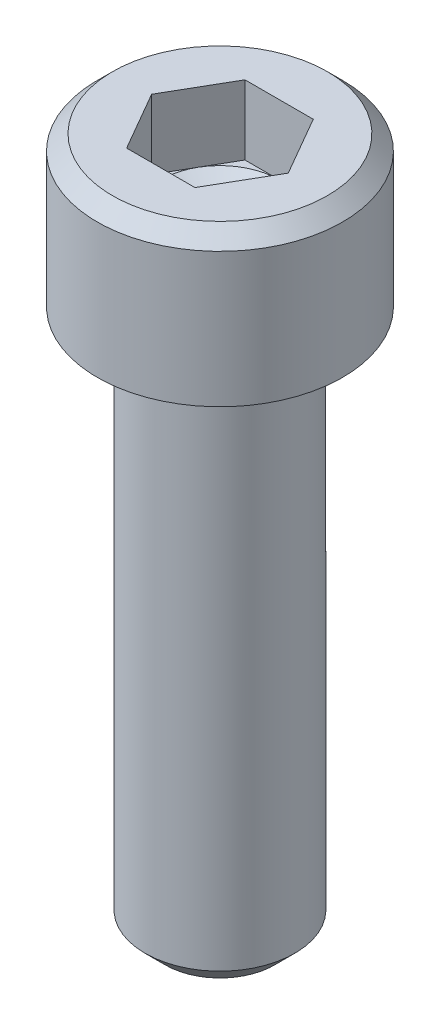
SolidWorks part; units mm, degrees
material "Alloy Steel"
ref_plane "Front Plane" through (0, 0, 0) normal (0, 0, 1) x (1, 0, 0)
ref_plane "Top Plane" through (0, 0, 0) normal (0, 1, 0) x (1, 0, 0)
ref_plane "Right Plane" through (0, 0, 0) normal (1, 0, 0) x (0, 0, -1)
sketch "Sketch1" plane through (0, 0, 0) normal (0, 0, 1) x (1, 0, 0)
  line L0 (2.8702, 3.5052) -> (0, 3.5052)
  line L1 (0, 3.5052) -> (0, 0)
  line L2 (0, 0) -> (2.8702, 0)
  line L3 (2.8702, 0) -> (2.8702, 3.5052)
  line L4 (0, 3.5052) -> (0, 0) construction
revolve "Revolve1" add sketch "Sketch1" angle 360 about L4 reverse direction yes
sketch "Sketch2" plane through (0, 0, 0) normal (0, -1, 0) x (1, 0, 0)
  circle A0 centre (0, 0) radius 1.7526
extrude "Boss-Extrude1" add sketch "Sketch2" along normal blind 12.7
sketch "Sketch3" plane through (0, 3.5052, 0) normal (0, 1, 0) x (-1, 0, 0)
  line L0 (-0.7992, 1.3843) -> (-1.5985, 0)
  line L1 (-1.5985, 0) -> (-0.7992, -1.3843)
  line L2 (-0.7992, -1.3843) -> (0.7992, -1.3843)
  line L3 (0.7992, -1.3843) -> (1.5985, 0)
  line L4 (1.5985, 0) -> (0.7992, 1.3843)
  line L5 (0.7992, 1.3843) -> (-0.7992, 1.3843)
extrude "Cut-Extrude1" cut sketch "Sketch3" against normal blind 1.6256
sketch "Sketch4" plane through (0, 0, 0) normal (0, 0, 1) x (1, 0, 0)
  line L0 (1.3843, 1.8796) -> (0, 1.8796)
  line L1 (0, 1.8796) -> (0, 1.0804)
  line L2 (0, 1.0804) -> (1.3843, 1.8796)
  line L3 (0, 1.8796) -> (0, 1.0803) construction
revolve "Cut-Revolve1" cut sketch "Sketch4" angle 360 about L3 reverse direction yes
chamfer "Chamfer1" distance 0.4724 angle 45 1 edges at (0, -12.7, -1.7526)
chamfer "Chamfer2" distance 0.3556 angle 45 1 edges at (0, 3.5052, -2.8702)
fillet "Fillet1" radius 0.254 1 edges at (0, 0, -1.7526) tangent propagation no
